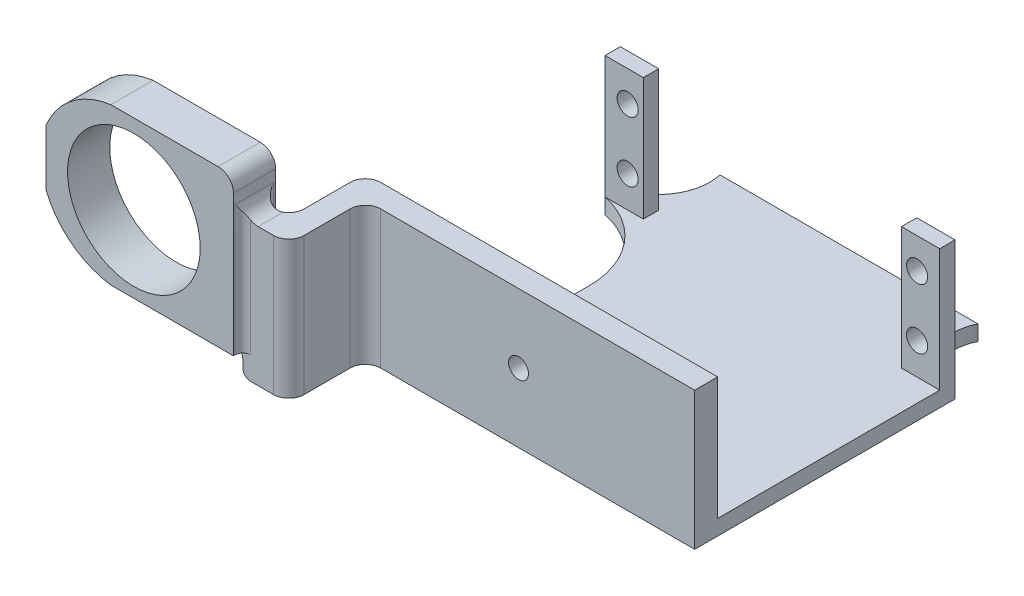
SolidWorks part; units mm, degrees
other "Markup1"
sketch "Sketch5" plane through (-1373.3675, 18.5, -401.6604) normal (0.7238, 0.4704, -0.5049) x (0.4214, -0.8807, -0.2164)
ref_plane "Front Plane" through (0, 0, 0) normal (0, 0, 1) x (1, 0, 0)
ref_plane "Top Plane" through (0, 0, 0) normal (0, 1, 0) x (1, 0, 0)
ref_plane "Right Plane" through (0, 0, 0) normal (1, 0, 0) x (0, 0, -1)
sketch "Sketch2" plane through (0, 0, 0) normal (0, 1, 0) x (1, 0, 0)
  line L1 (-1428.8835, 402.9304) -> (-1373.3675, 402.9304)
  line L2 (-1428.8835, 402.9304) -> (-1428.8835, 371.1804)
  line L3 (-1428.8835, 371.1804) -> (-1373.3675, 371.1804)
  line L4 (-1373.3675, 402.9304) -> (-1373.3675, 371.1804)
  dimension "D1" = 55.516
  dimension "D2" = 31.75
extrude "Boss-Extrude1" add sketch "Sketch2" along normal blind 2.54
sketch "Sketch4" plane through (0, 0, 0) normal (0, -1, 0) x (1, 0, 0)
  line L8 (-1373.3675, -402.9304) -> (-1428.8835, -402.9304) construction
  line L9 (-1373.3675, -402.9304) -> (-1379.7175, -402.9304)
  line L10 (-1373.3675, -402.9304) -> (-1373.3675, -405.4704)
  line L11 (-1373.3675, -405.4704) -> (-1379.7175, -405.4704)
  line L12 (-1379.7175, -402.9304) -> (-1379.7175, -405.4704)
  line L17 (-1422.5175, -402.9304) -> (-1428.8675, -402.9304)
  line L18 (-1422.5175, -402.9304) -> (-1422.5175, -405.4704)
  line L19 (-1422.5175, -405.4704) -> (-1428.8675, -405.4704)
  line L20 (-1428.8675, -402.9304) -> (-1428.8675, -405.4704)
  dimension "D1" = 55.5
  dimension "D2" = 6.35
  dimension "D3" = 2.54
  dimension "D4" = 6.35
  dimension "D5" = 2.54
extrude "Boss-Extrude7" add sketch "Sketch4" against normal blind 22.86
sketch "Sketch29" plane through (0, 0, -371.1804) normal (0, 0, 1) x (1, 0, 0)
  line L1 (-1428.8835, 2.54) -> (-1373.3675, 2.54)
  line L2 (-1428.8835, 2.54) -> (-1428.8835, 0)
  line L3 (-1428.8835, 0) -> (-1373.3675, 0)
  line L4 (-1373.3675, 2.54) -> (-1373.3675, 0)
extrude "Boss-Extrude12" add sketch "Sketch29" along normal blind 5.08
sketch "Sketch31" plane through (0, 0, 0) normal (0, -1, 0) x (1, 0, 0)
  line L1 (-1373.3675, -366.1004) -> (-1431.7875, -366.1004)
  line L2 (-1373.3675, -366.1004) -> (-1373.3675, -362.2904)
  line L3 (-1373.3675, -362.2904) -> (-1431.7875, -362.2904)
  line L4 (-1431.7875, -366.1004) -> (-1431.7875, -362.2904)
  line L5 (-1431.7875, -362.2904) -> (-1427.9775, -362.2904)
  line L6 (-1431.7875, -362.2904) -> (-1431.7875, -353.4004)
  line L7 (-1431.7875, -353.4004) -> (-1427.9775, -353.4004)
  line L8 (-1427.9775, -362.2904) -> (-1427.9775, -353.4004)
  line L9 (-1427.9775, -353.4004) -> (-1435.5975, -353.4004)
  line L10 (-1427.9775, -353.4004) -> (-1427.9775, -349.5904)
  line L11 (-1427.9775, -349.5904) -> (-1435.5975, -349.5904)
  line L12 (-1435.5975, -353.4004) -> (-1435.5975, -349.5904)
  line M11 (-1373.3675, -366.1004) -> (-1428.8835, -366.1004)
  dimension "D1" = 58.42
  dimension "D2" = 3.81
  dimension "D3" = 3.81
  dimension "D4" = 3.81
  dimension "D5" = 7.62
  dimension "D6" = 8.89
extrude "Boss-Extrude13" add sketch "Sketch31" against normal blind 22.86 contours L4 L1 L2 L3 M11 | L3 L8 L7 L6 | L12 L9 L7 L10 L11 region at (-1402.5775, 0, -364.1954) region at (-1429.8825, 0, -357.8454) region at (-1431.7875, 0, -351.4954)
sketch "Sketch32" plane through (-1435.5975, 0, 0) normal (-1, 0, 0) x (0, 0, 1)
  line L1 (-355.026, 29.718) -> (-348.026, 29.718)
  line L2 (-355.026, 29.718) -> (-355.026, 3.81)
  line L3 (-355.026, 3.81) -> (-348.026, 3.81)
  line L4 (-348.026, 29.718) -> (-348.026, 3.81)
  line L5 (-353.4004, 0) -> (-349.5904, 0) construction
  line L6 (-353.4004, 22.86) -> (-349.5904, 22.86) construction
  line L7 (-353.4004, 22.86) -> (-353.4004, 0) construction
  dimension "D1" = 7
  dimension "D2" = 6.858
  dimension "D3" = 3.81
  dimension "D4" = 1.6256
extrude "Boss-Extrude14" add sketch "Sketch32" along normal blind 31.75
sketch "Sketch33" plane through (0, 0, -362.2904) normal (0, 0, 1) x (1, 0, 0)
  line L0 (-1373.3675, 22.86) -> (-1427.9775, 22.86) construction
  line L1 (-1373.3675, 22.86) -> (-1373.3675, 0) construction
  circle A0 centre (-1402.5775, 11.43) radius 1.65
  dimension "D1" = 3.3
  dimension "D6" = 11.43
  dimension "D7" = 29.21
extrude "Cut-Extrude5" cut sketch "Sketch33" against normal blind 9.144
sketch "Sketch36" plane through (0, 0, -405.4704) normal (0, 0, -1) x (-1, 0, 0)
  line L0 (1428.8675, 22.86) -> (1428.8675, 0) construction
  line L1 (1373.3675, 22.86) -> (1373.3675, 0) construction
  line L4 (1428.8675, 22.86) -> (1422.5175, 22.86) construction
  line L6 (1379.7175, 22.86) -> (1373.3675, 22.86) construction
  circle A0 centre (1425.1175, 17.78) radius 1.75
  circle A1 centre (1425.1175, 7.78) radius 1.75
  circle A2 centre (1377.1175, 17.78) radius 1.75
  circle A3 centre (1377.1175, 7.78) radius 1.75
  dimension "D1" = 3.5
  dimension "D2" = 10
  dimension "D3" = 3.75
  dimension "D4" = 3.75
  dimension "D5" = 3.75
  dimension "D6" = 10
  dimension "D7" = 5.08
  dimension "D8" = 5.08
extrude "Cut-Extrude7" cut sketch "Sketch36" against normal blind 2.54
sketch "Sketch37" plane through (0, 0, -402.9304) normal (0, 0, -1) x (-1, 0, 0)
  line L1 (1379.7175, 2.54) -> (1422.5175, 2.54)
  line L2 (1379.7175, 2.54) -> (1379.7175, 0)
  line L3 (1379.7175, 0) -> (1422.5175, 0)
  line L4 (1422.5175, 2.54) -> (1422.5175, 0)
extrude "Boss-Extrude15" add sketch "Sketch37" along normal blind 12.7
sketch "Sketch38" plane through (0, 0, -405.4704) normal (0, 0, -1) x (-1, 0, 0)
  line L0 (1379.7175, 0) -> (1373.3675, 0) construction
  line L1 (1373.3675, 0) -> (1428.8675, 0)
  line L2 (1373.3675, 0) -> (1373.3675, 2.54)
  line L3 (1373.3675, 2.54) -> (1428.8675, 2.54)
  line L4 (1428.8675, 0) -> (1428.8675, 2.54)
  line L5 (1428.8675, 22.86) -> (1428.8675, 0) construction
  dimension "D1" = 2.54
extrude "Boss-Extrude16" add sketch "Sketch38" along normal blind 6.35
sketch "Sketch46" plane through (0, 2.54, 0) normal (0, 1, 0) x (1, 0, 0)
  line L5 (-1422.5175, 415.6304) -> (-1379.7175, 415.6304) construction
  line L6 (-1422.5175, 415.6304) -> (-1428.8675, 415.6304)
  line L9 (-1428.8675, 415.6304) -> (-1428.8675, 405.4704)
  line L11 (-1373.3675, 366.1004) -> (-1428.8835, 366.1004) construction
  line L12 (-1417.4371, 366.1004) -> (-1428.8835, 366.1004)
  line L15 (-1417.4371, 388.8461) -> (-1417.4371, 366.1004)
  line L16 (-1373.3675, 405.4704) -> (-1373.3675, 415.6304)
  line L17 (-1373.3675, 415.6304) -> (-1379.7175, 415.6304)
  line L18 (-1428.8835, 402.9304) -> (-1428.8835, 366.1004)
  arc A1 (-1379.7175, 415.6304) -> (-1373.3675, 405.4704) centre (-1373.4842, 412.4618) ccw
  arc A3 (-1422.5175, 415.6304) -> (-1428.8675, 405.4704) centre (-1430.7725, 413.7254) cw
  arc A4 (-1417.4371, 388.8461) -> (-1428.8835, 402.9304) centre (-1431.8254, 388.8461) ccw
extrude "Cut-Extrude19" cut sketch "Sketch46" against normal blind 17.78
fillet "Fillet9" radius 2.54 1 edges at (-1417.4371, 1.27, -366.1004)
fillet "Fillet11" radius 2.54 1 edges at (-1431.7875, 11.43, -353.4004)
fillet "Fillet12" radius 2.54 1 edges at (-1427.9775, 11.43, -362.2904)
fillet "Fillet13" radius 2.54 2 edges at (-1427.9775, 11.43, -349.5904) (-1431.7875, 11.43, -366.1004)
sketch "Sketch47" plane through (0, 0, -348.026) normal (0, 0, 1) x (1, 0, 0)
  line L1 (-1467.3475, 3.81) -> (-1467.3475, 29.718) construction
  line L3 (-1467.3475, 3.81) -> (-1435.5975, 3.81) construction
  circle A0 centre (-1452.1075, 16.51) radius 11
  dimension "D1" = 22
  dimension "D2" = 15.24
  dimension "D3" = 12.7
extrude "Cut-Extrude21" cut sketch "Sketch47" against normal blind 7.112
fillet "Fillet17" radius 1.27 2 edges at (-1435.5975, 0, -351.4954) (-1435.5975, 3.81, -351.4954)
fillet "Fillet18" radius 1.27 2 edges at (-1435.5975, 13.335, -353.4004) (-1435.5975, 13.335, -349.5904)
fillet "Fillet19" radius 2.54 2 edges at (-1435.5975, 29.718, -351.526) (-1435.5975, 22.86, -351.4954)
sketch "Sketch51" plane through (0, 0, -348.026) normal (0, 0, 1) x (1, 0, 0)
  line L0 (-1467.3475, 16.764) -> (-1467.3475, 19.304)
  line L1 (-1467.3475, 3.81) -> (-1435.5975, 3.81) construction
  line L5 (-1467.3475, 16.764) -> (-1467.3475, 14.224)
  line L7 (-1467.3475, 3.81) -> (-1467.3475, 29.718) construction
  line L10 (-1467.3475, 29.718) -> (-1438.1375, 29.718) construction
  line L11 (-1467.3475, 14.224) -> (-1467.3475, 3.81)
  line L12 (-1467.3475, 3.81) -> (-1455.9175, 3.81)
  line L13 (-1455.9175, 29.718) -> (-1467.3475, 29.718)
  line L14 (-1467.3475, 29.718) -> (-1467.3475, 19.304)
  line L15 (-1467.3475, 29.718) -> (-1455.9175, 29.718)
  arc A1 (-1467.3475, 14.224) -> (-1455.9175, 3.81) centre (-1454.169, 17.2086) ccw
  arc A2 (-1455.9175, 29.718) -> (-1467.3475, 19.304) centre (-1454.0781, 16.2196) ccw
  point P14 (-1455.9175, 3.81)
  line M7 (-1438.1375, 29.718) -> (-1467.3475, 29.718)
  line M8 (-1467.3475, 29.718) -> (-1467.3475, 3.81)
  line M9 (-1467.3475, 3.81) -> (-1435.5975, 3.81)
  dimension "D1" = 2.54
  dimension "D2" = 2.54
  dimension "D3" = 11.43
extrude "Cut-Extrude24" cut sketch "Sketch51" against normal blind 7.62 contours A2 M7 M8 | A1 M8 M9 region at (-1464.4617, 26.9987, -348.026) region at (-1464.4735, 6.5211, -348.026)
sketch "Sketch52" plane through (0, 0, -348.026) normal (0, 0, 1) x (1, 0, 0)
  line L5 (-1466.6802, 12.1045) -> (-1466.6802, 21.3944)
  line L6 (-1466.6802, 21.3944) -> (-1467.3475, 21.3944)
  line L7 (-1467.3475, 21.3944) -> (-1467.3475, 12.1045)
  line L9 (-1467.3475, 12.1045) -> (-1466.6802, 12.1045)
  arc A2 (-1467.3475, 14.224) -> (-1455.9175, 3.81) centre (-1454.169, 17.2086) ccw construction
  arc A3 (-1455.9175, 29.718) -> (-1467.3475, 19.304) centre (-1454.0781, 16.2196) ccw construction
extrude "Cut-Extrude25" cut sketch "Sketch52" against normal blind 7.62
equation "\"0.250.10in\"=0.34"
